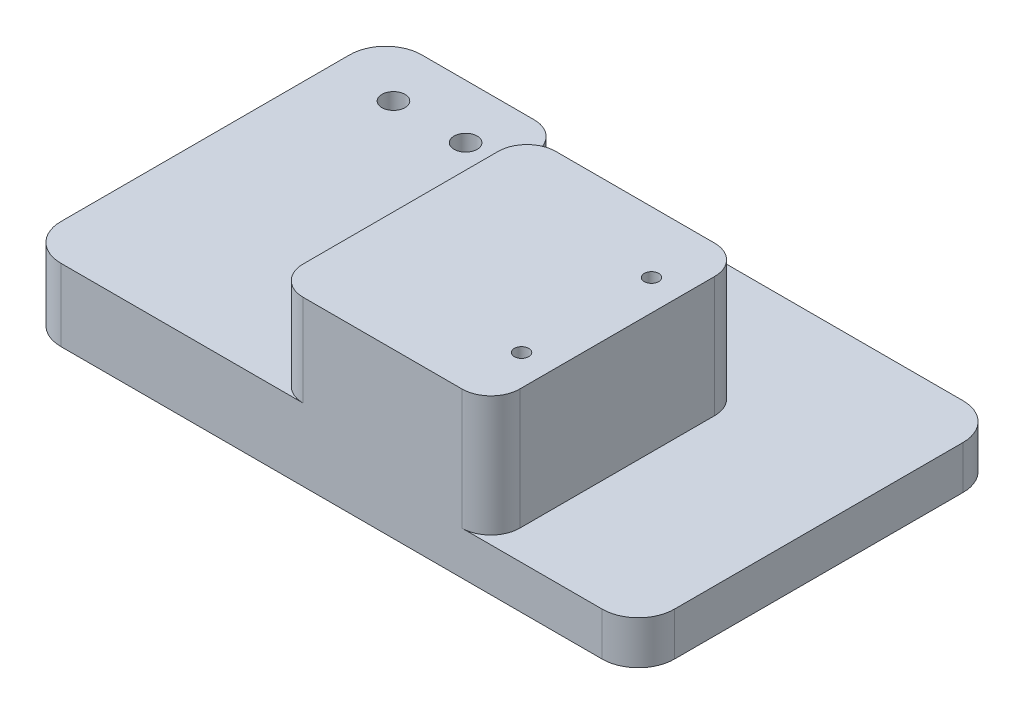
SolidWorks part; units mm, degrees
ref_plane "Front Plane" through (0, 0, 0) normal (0, 0, 1) x (1, 0, 0)
ref_plane "Top Plane" through (0, 0, 0) normal (0, 1, 0) x (1, 0, 0)
ref_plane "Right Plane" through (0, 0, 0) normal (1, 0, 0) x (0, 0, -1)
sketch "Sketch1" plane through (0, 0, 0) normal (0, 1, 0) x (1, 0, 0)
  line L1 (0, 0) -> (85, 0)
  line L2 (0, 0) -> (0, 50)
  line L3 (0, 50) -> (85, 50)
  line L4 (85, 0) -> (85, 50)
extrude "Boss-Extrude1" add sketch "Sketch1" along normal blind 6
sketch "Sketch2" plane through (0, 6, 0) normal (0, 1, 0) x (1, 0, 0)
  line L1 (85, 50) -> (0, 50) construction
  line L5 (0, 0) -> (85, 0) construction
  line L8 (0, 0) -> (0, 50)
  line L9 (0, 50) -> (24.5743, 50)
  line L10 (24.5743, 50) -> (24.5743, 35)
  line L11 (24.5743, 35) -> (9.5743, 35)
  line L12 (9.5743, 35) -> (9.5743, 0)
  line L13 (9.5743, 0) -> (0, 0)
extrude "Boss-Extrude2" add sketch "Sketch2" along normal blind 4
sketch "Sketch4" plane through (0, 10, 0) normal (0, 1, 0) x (1, 0, 0)
  line L0 (24.5743, 42.5) -> (18.5743, 42.5) construction
  line L1 (24.5743, 35) -> (24.5743, 50) construction
  line L2 (18.5743, 42.5) -> (8.5743, 42.5) construction
  circle A0 centre (18.5743, 42.5) radius 1.6
  circle A1 centre (8.5743, 42.5) radius 1.6
  dimension "D1" = 10
extrude "Cut-Extrude2" cut sketch "Sketch4" against normal blind 11
sketch "Sketch5" plane through (0, 6, 0) normal (0, 1, 0) x (1, 0, 0)
  line L1 (9.5743, 35) -> (9.5743, 0)
  line L5 (9.5743, 0) -> (64.5743, 0)
  line L6 (9.5743, 0) -> (85, 0) construction
  line L7 (64.5743, 0) -> (64.5743, 35)
  line L8 (64.5743, 35) -> (9.5743, 35)
extrude "Boss-Extrude3" add sketch "Sketch5" along normal blind 16.7
fillet "Fillet1" radius 5 4 edges at (85, 3, -50) (85, 3, 0) (0, 5, -50) (0, 5, 0)
sketch "Sketch6" plane through (0, 22.7, 0) normal (0, 1, 0) x (1, 0, 0)
  line L0 (64.5743, 17.5) -> (60.3243, 17.5) construction
  line L1 (64.5743, 0) -> (64.5743, 35) construction
  line L2 (60.3243, 17.5) -> (60.3243, 26.5) construction
  circle A0 centre (60.3243, 26.5) radius 1
  circle A1 centre (60.3243, 8.5) radius 1
extrude "Cut-Extrude3" cut sketch "Sketch6" against normal blind 10
sketch "Sketch7" plane through (0, 22.7, 0) normal (0, 1, 0) x (1, 0, 0)
  line L0 (9.5743, 35) -> (34.5743, 35)
  line L1 (64.5743, 35) -> (9.5743, 35) construction
  line L2 (34.5743, 35) -> (34.5743, 0)
  line L3 (9.5743, 0) -> (64.5743, 0) construction
  line L4 (34.5743, 0) -> (9.5743, 0)
  line L5 (9.5743, 0) -> (9.5743, 35)
extrude "Cut-Extrude4" cut sketch "Sketch7" against normal up to surface (12.7 mm away) up to face at (18.5743, 10, -40.9)
fillet "Fillet3" radius 4 4 edges at (64.5743, 14.35, 0) (64.5743, 14.35, -35) (34.5743, 16.35, -35) (34.5743, 16.35, 0)
fillet "Fillet4" radius 4 1 edges at (24.5743, 8, -35)
fillet "Fillet5" radius 4 1 edges at (24.5743, 8, -50)
